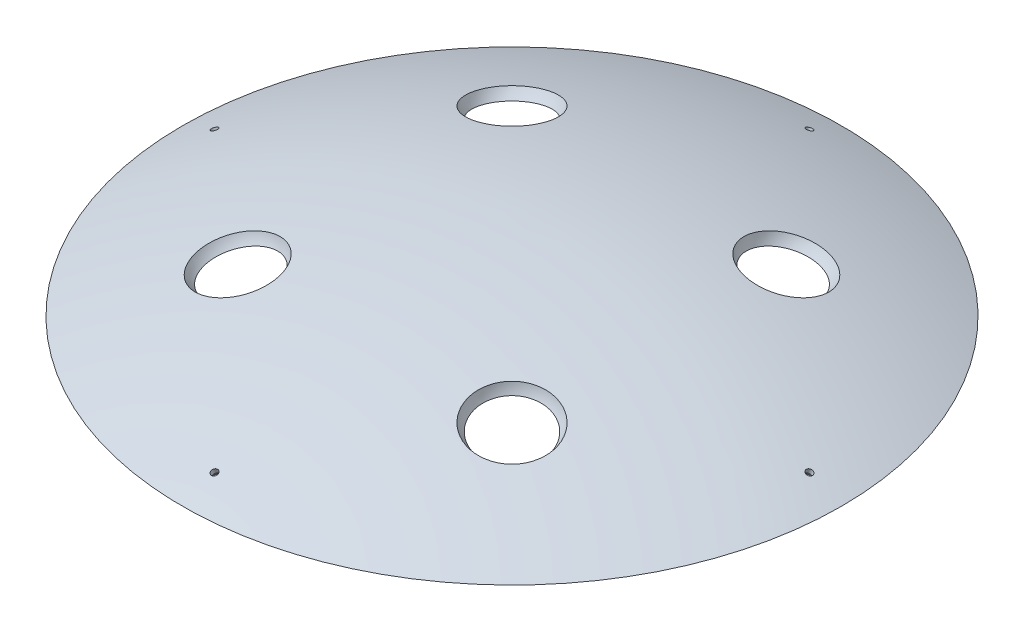
SolidWorks part; units mm, degrees
ref_plane "Front Plane" through (0, 0, 0) normal (0, 0, 1) x (1, 0, 0)
ref_plane "Top Plane" through (0, 0, 0) normal (0, 1, 0) x (1, 0, 0)
ref_plane "Right Plane" through (0, 0, 0) normal (1, 0, 0) x (0, 0, -1)
sketch "Sketch1" plane through (0, 0, 0) normal (0, 0, 1) x (1, 0, 0)
  line L0 (-150, 394.9445) -> (-150, 372.9445)
  line L1 (-150, 372.9445) -> (-100.1531, 349.7005)
  line L2 (0, 394.9445) -> (0, 544.9445)
  line L3 (0, 394.9445) -> (0, 370.6385)
  line L4 (-141.8706, 372.4638) -> (-96.4504, 351.284)
  line L9 (-100.1531, 349.7005) -> (-96.4504, 348.0288)
  line L10 (0, 370.6385) -> (0, 367.6385)
  line L12 (3, 394.9445) -> (3, 367.6203) construction
  line L13 (-153, 371.0333) -> (-100.1883, 346.4068) construction
  line L14 (-153, 394.9445) -> (-153, 371.0333) construction
  line L15 (3, 394.9445) -> (3, 547.9151) construction
  arc A0 (0, 370.6385) -> (-100.1531, 349.7005) centre (0, 120.6385) ccw
  arc A1 (0, 544.9445) -> (-150, 394.9445) centre (0, 394.9445) ccw
  arc A2 (0, 367.6385) -> (-96.4504, 348.0288) centre (0, 120.6385) ccw
  arc A4 (3, 367.6203) -> (-100.1883, 346.4068) centre (0, 120.6385) ccw construction
  arc A5 (3, 547.9151) -> (-153, 394.9445) centre (0, 394.9445) ccw construction
  dimension "D1" = 500
  dimension "D2" = 300
  dimension "D3" = 22
  dimension "D4" = 55
  dimension "D5" = 115
  dimension "D6" = 3
  dimension "D7" = 3
revolve "Revolve1" add sketch "Sketch1" angle 360 about L2 region at (-97.9012, 349.5557, 0)
sketch "Sketch3" plane through (0, 0, 0) normal (0, 0, 1) x (1, 0, 0)
  line L0 (-150, 372.9445) -> (-100.1531, 349.7005)
  line L1 (-150, 372.9445) -> (-150, 394.9445)
  line L2 (-147, 374.8557) -> (-147, 394.9445)
  line L3 (-147, 374.8557) -> (-98.8852, 352.4194)
  line L4 (-98.8852, 352.4194) -> (-96.4504, 351.284)
  line L5 (0, 120.6385) -> (-90.3797, 353.7297)
  line L6 (0.9324, 121.0001) -> (-89.4474, 354.0913)
  line L7 (1.8647, 121.3616) -> (-88.515, 354.4528)
  circle A0 centre (0, 120.6385) radius 250
  arc A1 (100.1531, 349.7005) -> (-100.1531, 349.7005) centre (0, 120.6385) ccw construction
  arc A2 (-135.5683, 330.6891) -> (-150, 394.8277) centre (0, 394.8861) ccw
  circle A3 centre (0, 120.6385) radius 247
  circle A4 centre (0.9324, 121.0001) radius 248.5
  dimension "D1" = 500
  dimension "D2" = 300
  dimension "D10" = 497
  dimension "D3" = 22
  dimension "D4" = 55
  dimension "D5" = 115
  dimension "D7" = 1.5
  dimension "D11" = 1
  dimension "D6" = 3
  dimension "D8" = 1
  dimension "D9" = 3
revolve "Cut-Revolve1" cut sketch "Sketch3" angle 360 about L5 region at (-89.6424, 353.2105, 0) region at (-89.0997, 351.8121, 0) region at (-88.1666, 352.1718, 0)
sketch "Sketch4" plane through (0, 0, 0) normal (0, 0, 1) x (1, 0, 0)
  line L0 (0, 0) -> (0, 436.9518)
pattern_circular "CirPattern2" count 4 every 90 about axis through (0, 0, 0) along (0, 1, 0) of "Cut-Revolve1"
ref_plane "Plane1" through (0, 0, 0) normal (0.7071, 0, 0.7071) x (0, 1, 0)
sketch "Sketch5" plane through (0, 0, 0) normal (0.7071, 0, 0.7071) x (0, 1, 0)
  line L0 (0, 0) -> (436.9518, 0) construction
  line L1 (354.9885, 60) -> (388.4674, 60)
  line L2 (354.9885, 60) -> (309.9583, 60)
  arc A0 (360.5517, 70.2969) -> (366.0953, 47.4445) centre (120.6385, 0) ccw
  arc A1 (349.7005, -100.1531) -> (349.7005, 100.1531) centre (120.6385, 0) ccw construction
  arc A3 (354.9885, 60) -> (380.2885, 60) centre (367.6385, 60) ccw
  point P7 (370.6385, 0)
  dimension "D1" = 500
  dimension "D2" = 25.3
  dimension "D3" = 60
  dimension "D4" = 3
revolve "Cut-Revolve5" cut sketch "Sketch5" angle 360 about L2 region at (-38.6301, 367.6385, 38.6301)
pattern_circular "CirPattern3" count 4 every 90 about axis through (0, 0, 0) along (0, 1, 0) of "Cut-Revolve5"
scale "Scale1" bodies to scale 107 scale about origin uniform scaling yes scale factor 0.8
